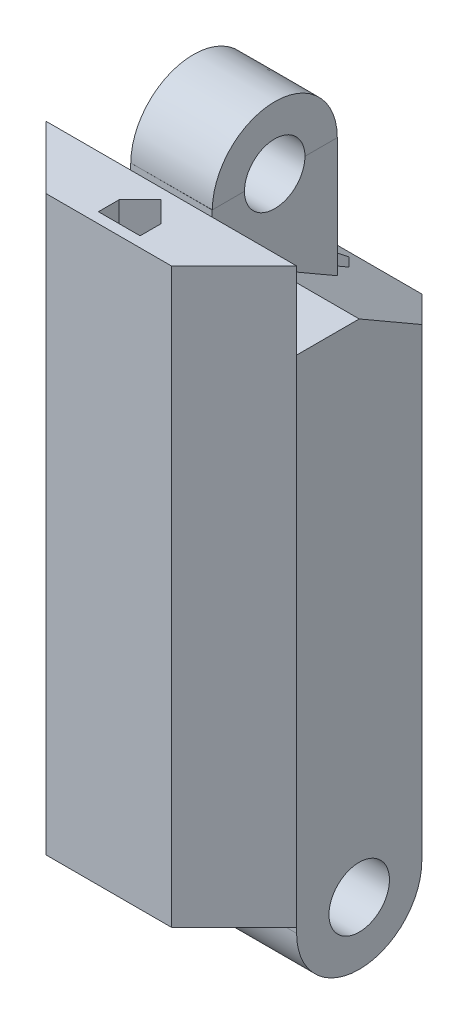
SolidWorks part; units mm, degrees
ref_plane "Front Plane" through (0, 0, 0) normal (0, 0, 1) x (1, 0, 0)
ref_plane "Top Plane" through (0, 0, 0) normal (0, 1, 0) x (1, 0, 0)
ref_plane "Right Plane" through (0, 0, 0) normal (1, 0, 0) x (0, 0, -1)
sketch "Sketch2" plane through (0, 0, 0) normal (0, 1, 0) x (1, 0, 0)
  line L0 (-3, 6) -> (3, 6)
  line L1 (3, 6) -> (6, 3)
  line L2 (6, 3) -> (6, -3)
  line L3 (6, -3) -> (3, -6)
  line L4 (3, -6) -> (-3, -6)
  line L5 (-3, -6) -> (-6, -3)
  line L6 (-6, -3) -> (-6, 3)
  line L7 (-6, 3) -> (-3, 6)
  point P2 (0, -6)
  point P9 (0, 6)
  point P12 (-6, 0)
  point P13 (6, 0)
  dimension "D1" = 12
  dimension "D2" = 12
  dimension "D3" = 6
  dimension "D4" = 6
  dimension "D5" = 6
extrude "Boss-Extrude1" add sketch "Sketch2" along normal mid plane 20 contours L7 L0 L1 L2 L3 L4 L5 L6
sketch "Sketch5" plane through (0, 0, 0) normal (1, 0, 0) x (0, 0, -1)
  line L1 (3, 10) -> (-3, 10) construction
  line L2 (0, 10) -> (6, 6.5359)
  line L3 (6, 10) -> (6, -10) construction
  line L4 (6, 6.5359) -> (6, 10)
  line L5 (6, 10) -> (0, 10)
  dimension "D1" = 30
extrude "Cut-Extrude2" cut sketch "Sketch5" against normal through all both and the other way through all
mirror "Mirror3" about plane through (0, 0, 0) normal (0, 1, 0) of "Cut-Extrude2"
sketch "Sketch6" plane through (0, -10, 0) normal (0, -1, 0) x (1, 0, 0)
  line L1 (-6, 3) -> (-2.1, 3)
  line L2 (-6, 3) -> (-6, -3)
  line L3 (-6, -3) -> (-2.1, -3)
  line L4 (-2.1, 3) -> (-2.1, -3)
  dimension "D1" = 3.9
extrude "Boss-Extrude3" add sketch "Sketch6" along normal mid plane 8
sketch "Sketch7" plane through (0, -14, 0) normal (0, -1, 0) x (1, 0, 0)
  line L0 (-6, 3) -> (-6, -3) construction
  line L1 (-6, 0) -> (-2.1, 0)
  line L2 (-6, 0) -> (-6, 3)
  line L3 (-6, 3) -> (-2.1, 3)
  line L4 (-2.1, 0) -> (-2.1, 3)
revolve "Revolve1" add sketch "Sketch7" angle 180 about L1
sketch "Sketch8" plane through (-6, 0, 0) normal (-1, 0, 0) x (0, 0, 1)
  line L0 (-3, -14) -> (3, -14) construction
sketch "Sketch9" plane through (-6, 0, 0) normal (-1, 0, 0) x (0, 0, 1)
  line L0 (-3, -14) -> (3, -14) construction
  circle A0 centre (0, -14) radius 1.45
  dimension "D1" = 2.9
extrude "Cut-Extrude3" cut sketch "Sketch9" against normal mid plane 10
mirror "Mirror5" about plane through (0, 0, 0) normal (1, 0, 0) of "Revolve1", "Boss-Extrude3", "Cut-Extrude3"
sketch "Sketch10" plane through (0, 10, 0) normal (0, 1, 0) x (1, 0, 0)
  line L0 (-6, -3) -> (6, -3) construction
  line L1 (-1.95, -3) -> (1.95, -3)
  line L2 (-1.95, -3) -> (-1.95, 3)
  line L3 (-1.95, 3) -> (1.95, 3)
  line L4 (1.95, -3) -> (1.95, 3)
  line L5 (-1.95, -3) -> (1.95, 3) construction
  line L6 (-1.95, 3) -> (1.95, -3) construction
  point P6 (0, 0)
  dimension "D1" = 3.9
extrude "Boss-Extrude4" add sketch "Sketch10" along normal mid plane 8
sketch "Sketch12" plane through (0, 14, 0) normal (0, 1, 0) x (1, 0, 0)
  line L0 (-1.95, 3) -> (-1.95, 0)
  line L3 (-1.95, 3) -> (1.95, 3)
  line L4 (1.95, 0.0037) -> (1.95, 3)
  line L5 (-1.95, 3) -> (-1.95, -3) construction
  line L6 (-1.95, 0) -> (1.95, 0.0037)
revolve "Revolve2" add sketch "Sketch12" angle 180 about L6
sketch "Sketch13" plane through (-1.95, 0, 0) normal (-1, 0, 0) x (0, 0, 1)
  line L0 (-3, 14) -> (3, 14) construction
  line L1 (0, 14) -> (3, 14) construction
sketch "Sketch14" plane through (-1.95, 0, 0) normal (-1, 0, 0) x (0, 0, 1)
  line L0 (-3, 14) -> (3, 14) construction
  circle A0 centre (0, 14) radius 1.45
  dimension "D1" = 2.9
extrude "Cut-Extrude4" cut sketch "Sketch14" against normal mid plane 10
sketch "Sketch17" plane through (0, 10, 0) normal (0, 1, 0) x (1, 0, 0)
  line L0 (-6, -3) -> (-1.95, -3)
  line L1 (-1.95, -3) -> (1.95, -3)
  line L2 (6, -3) -> (1.95, -3)
  line L3 (3, -6) -> (6, -3)
  line L4 (-6, -3) -> (-3, -6)
  line L5 (-3, -6) -> (3, -6)
extrude "Boss-Extrude7" add sketch "Sketch17" along normal blind 3.7
sketch "Sketch15" plane through (0, 0, 0) normal (0, 1, 0) x (1, 0, 0)
  line L0 (0, 5.5) -> (-1, 4.5)
  line L1 (-1, 4.5) -> (-1, 3.5)
  line L2 (-1, 3.5) -> (1, 3.5)
  line L3 (1, 3.5) -> (1, 4.5)
  line L4 (1, 4.5) -> (0, 5.5)
  line L6 (1, -4.5) -> (0, -3.5)
  line L7 (0, -3.5) -> (-1, -4.5)
  line L8 (-1, -4.5) -> (-1, -5.5)
  line L9 (-1, -5.5) -> (1, -5.5)
  line L10 (1, -5.5) -> (1, -4.5)
  line L12 (1.95, -3) -> (-1.95, -3) construction
  line L13 (1.95, 3) -> (-1.95, 3) construction
  dimension "D1" = 2
  dimension "D2" = 2
  dimension "D3" = 135
  dimension "D4" = 135
  dimension "D5" = 1
  dimension "D6" = 2
  dimension "D7" = 0.5
  dimension "D8" = 0.5
sketch "Sketch19" plane through (0, -10, 0) normal (0, -1, 0) x (1, 0, 0)
  line L0 (-6, 3) -> (-2.1, 3)
  line L1 (-2.1, 3) -> (2.1, 3)
  line L2 (2.1, 3) -> (6, 3)
  line L3 (6, 3) -> (3, 6)
  line L4 (3, 6) -> (-3, 6)
  line L5 (-3, 6) -> (-6, 3)
extrude "Boss-Extrude17" add sketch "Sketch19" along normal blind 3.75
extrude "Cut-Extrude6" cut sketch "Sketch15" against normal through all both and the other way through all
sketch "Sketch20" plane through (-1.95, 0, 0) normal (-1, 0, 0) x (0, 0, 1)
  line L0 (3, 14) -> (0.0001, 17)
  line L1 (0.0001, 17) -> (0.0001, 17.5375)
  line L2 (0.0001, 17.5375) -> (3, 17.5375)
  line L3 (3, 17.5375) -> (3.3716, 17.5375)
  line L4 (3.3716, 17.5375) -> (3.3716, 14)
  line L5 (3.3716, 14) -> (3, 14)
  ellipse E0 centre (0, 14) end of major axis (0, 11) minor radius 3 (3, 14) -> (-3, 14) ccw construction
